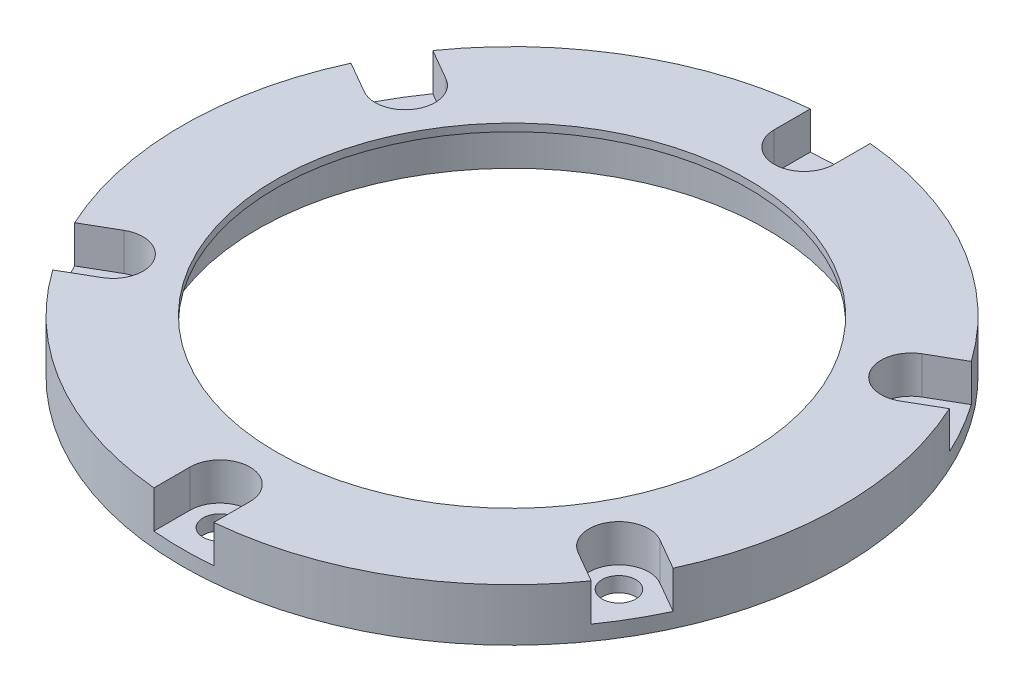
SolidWorks part; units mm, degrees
material "7075-T6, 플레이트 (SS)"
ref_plane "정면" through (0, 0, 0) normal (0, 0, 1) x (1, 0, 0)
ref_plane "윗면" through (0, 0, 0) normal (0, 1, 0) x (1, 0, 0)
ref_plane "우측면" through (0, 0, 0) normal (1, 0, 0) x (0, 0, -1)
sketch "스케치1" plane through (0, 0, 0) normal (0, 1, 0) x (1, 0, 0)
  circle A0 centre (0, 0) radius 44
  circle A1 centre (0, 0) radius 34
  dimension "D1" = 88
  dimension "D2" = 68
extrude "보스-돌출1" add sketch "스케치1" along normal blind 6
sketch "스케치2" plane through (0, 6, 0) normal (0, 1, 0) x (1, 0, 0)
  circle A0 centre (0, 0) radius 31.5
  circle A1 centre (0, 0) radius 44 construction
  circle A2 centre (0, 0) radius 44
  dimension "D1" = 63
extrude "보스-돌출2" add sketch "스케치2" along normal blind 1
sketch "스케치3" plane through (0, 7, 0) normal (0, 1, 0) x (1, 0, 0)
  circle A0 centre (0, 0) radius 39 construction
  point P3 (0, 39)
  dimension "D1" = 78
hole_wizard "M4 육각 소켓 머리 캡 나사용 카운터보어1" positions "스케치4" profile "스케치6" counterbore size "M4" standard "ISO" end condition through all
sketch "스케치4" plane through (0, 7, 0) normal (0, 1, 0) x (1, 0, 0)
  point P0 (0, 39)
sketch "스케치6" plane through (0, 7, -39) normal (1, 0, 0) x (0, 0, 1)
  line L0 (0, 0) -> (0, 7)
  line L1 (0, 7) -> (2.25, 7)
  line L3 (2.25, 7) -> (2.25, 5)
  line L4 (2.25, 5) -> (4, 5)
  line L5 (4, 5) -> (4, 0)
  line L7 (4, 0) -> (0, 0)
  line L11 (0, -6.35) -> (0, 107.95) construction
  dimension "관통 구멍 지름" = 4.5
  dimension "관통 구멍 깊이" = 7
  dimension "카운터보어 지름" = 8
  dimension "카운터보어 깊이" = 5
pattern_circular "원형 패턴1" count 6 over 360 about axis through (0, 6, 0) along (0, -1, 0) of "M4 육각 소켓 머리 캡 나사용 카운터보어1" reverse direction yes
fillet "필렛1" radius 0.3 1 edges at (0, 6, 34)
sketch "스케치7" plane through (0, 7, 0) normal (0, 1, 0) x (1, 0, 0)
  line L2 (-4, 39) -> (-4, 44)
  line L3 (-4, 44) -> (4, 44)
  line L4 (4, 39) -> (4, 44)
  circle A0 centre (0, 39) radius 4 construction
  circle A1 centre (0, 39) radius 4 construction
  arc A2 (4, 39) -> (-4, 39) centre (0, 39) ccw
  circle A3 centre (0, 0) radius 44 construction
extrude "컷-돌출1" cut sketch "스케치7" against normal mid plane 10
pattern_circular "원형 패턴2" count 6 over 360 about axis through (0, 6, 0) along (0, -1, 0) of "컷-돌출1" reverse direction yes
